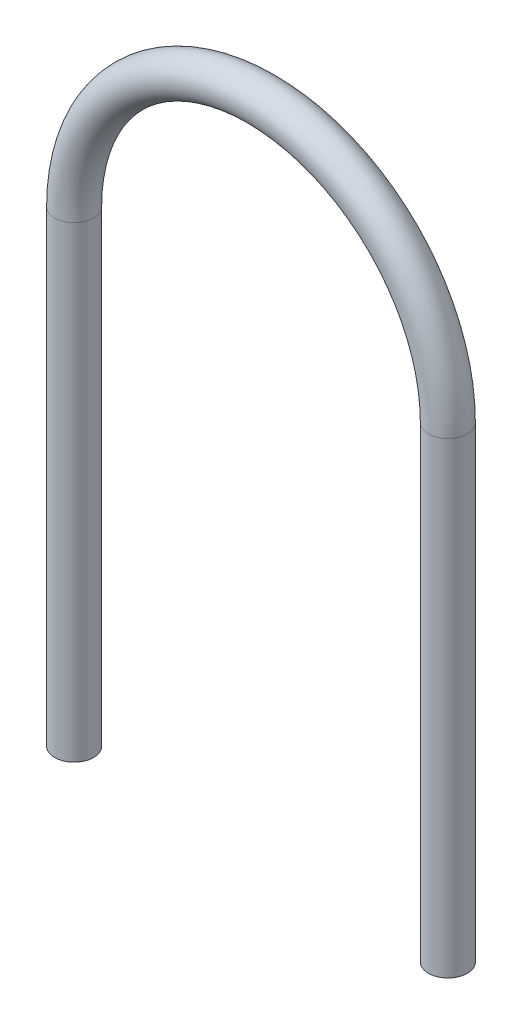
SolidWorks part; units mm, degrees
material "AISI 1020"
ref_plane "Front Plane" through (0, 0, 0) normal (0, 0, 1) x (1, 0, 0)
ref_plane "Top Plane" through (0, 0, 0) normal (0, 1, 0) x (1, 0, 0)
ref_plane "Right Plane" through (0, 0, 0) normal (1, 0, 0) x (0, 0, -1)
sketch "Sketch1" plane through (0, 0, 0) normal (0, 0, 1) x (1, 0, 0)
  line L0 (0, 0) -> (0, 76.2)
  line L1 (-54.61, 76.2) -> (-54.61, 0)
  arc A0 (0, 76.2) -> (-54.61, 76.2) centre (-27.305, 76.2) ccw
  dimension "D1" = 27.305
sketch "Sketch2" plane through (0, 0, 0) normal (0, 1, 0) x (1, 0, 0)
  line L0 (0, 0) -> (3.175, 0) construction
  circle A0 centre (3.175, 0) radius 3.175
  dimension "D1" = 6.35
sweep "Sweep1" add profiles "Sketch2" path "Sketch1"
ref_plane "Plane1" through (0, 76.2, 0) normal (0, -1, 0) x (1, 0, 0)
sketch "Sketch3" plane through (0, 76.2, 0) normal (0, -1, 0) x (1, 0, 0)
  line L0 (0, 0) -> (0, -2.2894)
  line L1 (0, -2.2894) -> (0.1416, -2.2894)
  line L2 (0.1416, -2.2894) -> (0.1416, 2.0391)
  line L3 (0.1416, 2.0391) -> (0, 2.0391)
  line L4 (0, 2.0391) -> (0, 0)
sketch "Sketch4" plane through (0, 0, 0) normal (0, 0, 1) x (1, 0, 0)
  line L0 (-54.61, 76.2) -> (0, 76.2) construction
  point P0 (-27.305, 76.2)
  point P5 (-27.305, 76.2)
sketch "Sketch6" plane through (0, 0, 0) normal (0, 0, 1) x (1, 0, 0)
  line L0 (-27.305, 88.9) -> (-27.305, 63.5)
  line L1 (-40.005, 76.2) -> (-14.605, 76.2)
  line L2 (-54.61, 76.2) -> (0, 76.2) construction
  point P7 (-27.305, 76.2)
  point P10 (-27.305, 76.2)
sketch "Sketch8" plane through (0, 76.2, 0) normal (0, -1, 0) x (1, 0, 0)
  line L0 (-27.305, 12.7) -> (-27.305, -12.7)
  point P2 (-27.305, 0)
